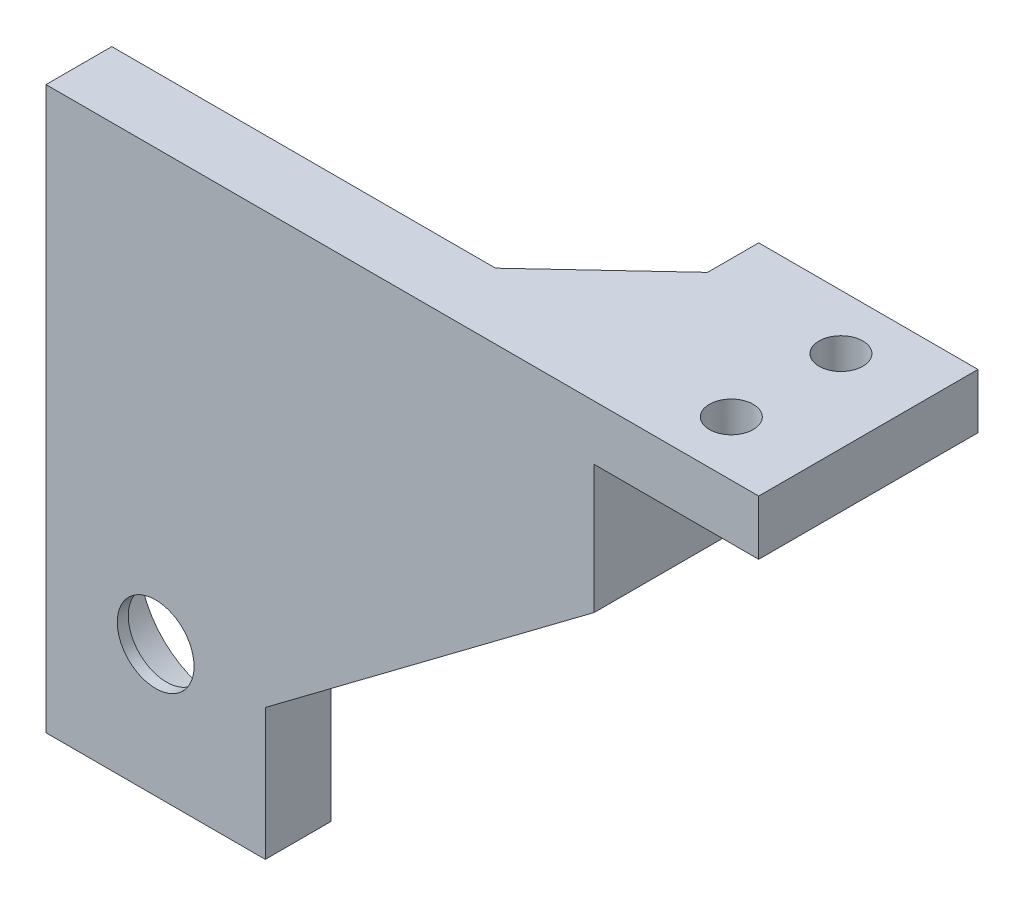
SolidWorks part; units mm, degrees
ref_plane "Front Plane" through (0, 0, 0) normal (0, 0, 1) x (1, 0, 0)
ref_plane "Top Plane" through (0, 0, 0) normal (0, 1, 0) x (1, 0, 0)
ref_plane "Right Plane" through (0, 0, 0) normal (1, 0, 0) x (0, 0, -1)
sketch "Sketch1" plane through (0, 0, 0) normal (0, 0, 1) x (1, 0, 0)
  circle A0 centre (0, 0) radius 7.5
  circle A1 centre (0, 0) radius 3.5
  circle A2 centre (0, 0) radius 10
  dimension "D1" = 15
  dimension "D2" = 20
  dimension "D3" = 7
extrude "Boss-Extrude1" add sketch "Sketch1" against normal up to surface (5 mm away) contours A2 A0 region at (-9.7172, 0, 0)
extrude "Boss-Extrude2" add sketch "Sketch1<3>" along normal blind 1 contours A0 A1 | A2 A0 region at (-7.2879, 0, 0) region at (-9.7172, 0, 0)
sketch "Sketch1<3>" plane through (0, 0, 0) normal (0, 0, 1) x (1, 0, 0) same geometry as "Sketch1"
sketch "Sketch2" plane through (0, 0, 1) normal (0, 0, 1) x (1, 0, 0)
  line L0 (10, 0) -> (40, 22.5)
  line L1 (40, 22.5) -> (40, 34.2)
  line L2 (40, 34.2) -> (-10, 34.2)
  line L3 (290, 34.2) -> (-110, 34.2) construction
  line L4 (-10, 34.2) -> (-10, 0)
  line L5 (-10, 0) -> (-10, -12)
  line L6 (-10, -12) -> (10, -12)
  line L7 (10, -12) -> (10, 0)
  line L9 (-10, 34.2) -> (55, 34.2)
  line L10 (-10, 34.2) -> (-10, 39.2)
  line L11 (-10, 39.2) -> (55, 39.2)
  line L12 (55, 34.2) -> (55, 39.2)
  line L13 (-10, 34.2) -> (55, 39.2) construction
  line L14 (-10, 39.2) -> (55, 34.2) construction
  circle A0 centre (0, 0) radius 10 construction
  circle A1 centre (0, 0) radius 10
  point P20 (22.5, 36.7)
  circle M4 centre (0, 0) radius 10
  dimension "D1" = 12
  dimension "D2" = 20
  dimension "D3" = 5
  dimension "D4" = 15
extrude "Boss-Extrude3" add sketch "Sketch2" against normal up to surface (6 mm away) contours L2 L4 L0 L1 M4 | L6 L7 L5 M4 | L9 L12 L11 L10 L2 region at (12.7734, 21.4272, 1) region at (9.7668, -6, 1) region at (22.5, 36.7, 1) up to face at (-10, 0, -5)
sketch "Sketch3" plane through (0, 39.2, 0) normal (0, 1, 0) x (1, 0, 0)
  line L0 (55, -1) -> (55, 19)
  line L1 (55, 19) -> (40, 19)
  line L2 (40, 19) -> (40, 5)
  line L3 (-10, 5) -> (55, 5) construction
  line L4 (40, 286) -> (40, -14) construction
  line L5 (-10, -1) -> (55, -1) construction
  line L6 (40, 19) -> (35, 19)
  line L7 (35, 19) -> (35, 5)
  line M4 (55, 5) -> (-10, 5)
  dimension "D1" = 20
  dimension "D2" = 5
extrude "Boss-Extrude4" add sketch "Sketch3" against normal up to surface (5 mm away) contours L1 L2 L0 M4 | L6 L7 L2 M4 region at (47.5, 39.2, -12) region at (37.5, 39.2, -12)
sketch "Sketch4" plane through (0, 39.2, 0) normal (0, 1, 0) x (1, 0, 0)
  line L0 (40, 19) -> (25, 5)
  line L1 (-10, 5) -> (35, 5) construction
  line L3 (55, 19) -> (35, 19) construction
  line L4 (40, 286) -> (40, -14) construction
  line L5 (40, 19) -> (40, -1)
  line L6 (-10, -1) -> (55, -1) construction
  line L7 (40, -1) -> (25, -1)
  line L8 (25, -1) -> (25, 5)
  point P15 (25, 4.9031)
  dimension "D1" = 10
extrude "Boss-Extrude6" add sketch "Sketch4" against normal up to surface (16.7 mm away) up to face at (25, 11.25, -2)
extrude "Boss-Extrude5" add sketch "Sketch3<3>" against normal up to surface (16.7 mm away) contours L6 L7 L2 M4 region at (37.5, 39.2, -12) up to face at (25, 11.25, -5.4)
sketch "Sketch3<3>" plane through (0, 39.2, 0) normal (0, 1, 0) x (1, 0, 0) same geometry as "Sketch3"
sketch "Sketch5" plane through (0, 39.2, 0) normal (0, 1, 0) x (1, 0, 0)
  line L0 (55, 19) -> (35, 19) construction
  line L1 (55, -1) -> (40, -1) construction
  line L2 (55, -1) -> (55, 19) construction
  line L3 (55, 19) -> (40, 19) construction
  line L4 (40, -1) -> (40, 19) construction
  line L5 (55, -1) -> (40, 19) construction
  line L6 (55, 19) -> (40, -1) construction
  line L7 (40, 286) -> (40, -14) construction
  line L8 (40, 9) -> (55, 9) construction
  circle A0 centre (47.5, 14) radius 2
  circle A1 centre (47.5, 14) radius 4 construction
  circle A2 centre (47.5, 4) radius 4 construction
  circle A3 centre (47.5, 4) radius 2
  point P4 (47.5, 9)
  dimension "D1" = 8
  dimension "D2" = 4
  dimension "D3" = 5
  dimension "D4" = 7.5
extrude "Cut-Extrude1" cut sketch "Sketch5" against normal through all
